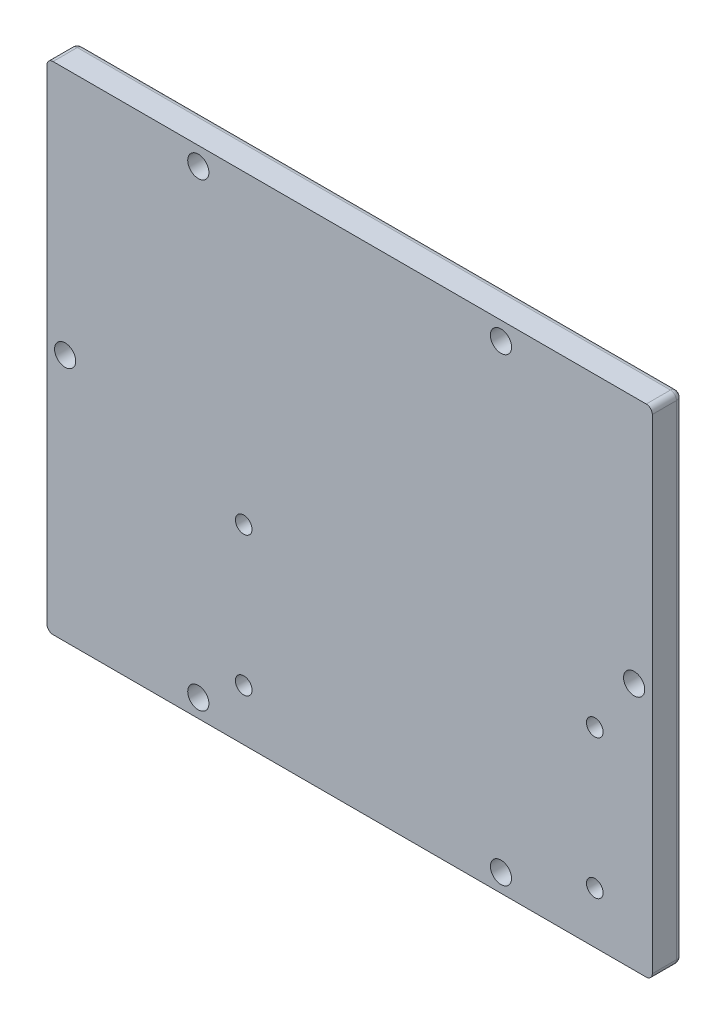
SolidWorks part; units mm, degrees
ref_plane "Plan de face" through (0, 0, 0) normal (0, 0, 1) x (1, 0, 0)
ref_plane "Plan de dessus" through (0, 0, 0) normal (0, 1, 0) x (1, 0, 0)
ref_plane "Plan de droite" through (0, 0, 0) normal (1, 0, 0) x (0, 0, -1)
sketch "Esquisse1" plane through (0, 0, 0) normal (0, 0, 1) x (1, 0, 0)
  line L1 (-50, -41) -> (50, -41)
  line L2 (-50, -41) -> (-50, 41)
  line L3 (-50, 41) -> (50, 41)
  line L4 (50, -41) -> (50, 41)
  line L5 (-50, -41) -> (50, 41) construction
  line L6 (-50, 41) -> (50, -41) construction
  point P0 (0, 0)
  dimension "D1" = 82
  dimension "D2" = 100
extrude "Boss.-Extru.1" add sketch "Esquisse1" along normal blind 5
sketch "Esquisse2" plane through (0, 0, 0) normal (0, 0, 1) x (1, 0, 0)
  line L0 (-81.9731, -38) -> (83.9393, -38) construction
  line L1 (-50, -41) -> (50, -41) construction
  line L2 (0, 0) -> (0, -49.9002) construction
  line L3 (-50, 41) -> (-50, -41) construction
  line L5 (-25, 38) -> (82.6895, 38) construction
  line L6 (50, 41) -> (-50, 41) construction
  circle A0 centre (-25, -38) radius 1.75
  circle A1 centre (25, -38) radius 1.75
  circle A2 centre (-25, 38) radius 1.75
  circle A3 centre (25, 38) radius 1.75
  dimension "D2" = 3.5
  dimension "D4" = 3
  dimension "D5" = 25
  dimension "D1" = 3
  dimension "D3" = 25
extrude "Enlèv. mat.-Extru.1" cut sketch "Esquisse2" along normal up to surface (5 mm away) up to face at (0, 0, 5)
sketch "Esquisse3" plane through (0, 0, 0) normal (0, 0, 1) x (1, 0, 0)
  line L0 (-84.0905, 0) -> (94.0725, 0) construction
  line L1 (47, 56.9426) -> (47, -50.5904) construction
  line L2 (50, -41) -> (50, 41) construction
  circle A0 centre (47, 0) radius 1.75
  dimension "D2" = 3.5
  dimension "D1" = 3
extrude "Enlèv. mat.-Extru.2" cut sketch "Esquisse3" along normal up to surface (5 mm away) up to face at (23.25, -38, 5)
mirror "Symétrie1" about plane through (0, 0, 0) normal (1, 0, 0) of "Enlèv. mat.-Extru.2"
sketch "Esquisse5" [suppressed] plane through (0, 0, 0) normal (0, 0, 1) x (1, 0, 0)
  line L1 (-30.25, -28.75) -> (30.25, -28.75)
  line L2 (-30.25, -28.75) -> (-30.25, 6.75)
  line L3 (-30.25, 6.75) -> (30.25, 6.75)
  line L4 (30.25, -28.75) -> (30.25, 6.75)
  line L5 (-30.25, -28.75) -> (30.25, 6.75) construction
  line L6 (-30.25, 6.75) -> (30.25, -28.75) construction
  line L7 (-50, -41) -> (50, -41) construction
  line L8 (50, -41) -> (50, 41) construction
  point P0 (0, -11)
  dimension "D1" = 60.5
  dimension "D2" = 35.5
  dimension "D3" = 19.75
  dimension "D4" = 30
extrude "Enlèv. mat.-Extru.4" [suppressed] cut sketch "Esquisse5" along normal up to surface (5 mm away)
sketch "Esquisse7" [suppressed] plane through (0, 0, 5) normal (0, 0, 1) x (1, 0, 0)
  line L0 (50, 41) -> (-50, 41) construction
  line L1 (-7, 11) -> (7, 11) construction
  line L2 (-7, 11) -> (-7, 21) construction
  line L3 (-7, 21) -> (7, 21) construction
  line L4 (7, 11) -> (7, 21) construction
  line L5 (-7, 11) -> (7, 21) construction
  line L6 (-7, 21) -> (7, 11) construction
  line L11 (50, -41) -> (50, 41) construction
  circle A3 centre (-7, 11) radius 1.5
  circle A4 centre (7, 11) radius 1.5
  circle A5 centre (-1.66, 20.3) radius 3.65
  dimension "D1" = 7.3
  dimension "D2" = 5.34
  dimension "D4" = 3
  dimension "D6" = 30
  dimension "D5" = 9.3
  dimension "D3" = 8.66
  dimension "D7" = 43
extrude "Enlèv. mat.-Extru.5" [suppressed] cut sketch "Esquisse7" against normal up to surface (5 mm away)
fillet "Congé1" [suppressed] radius 1
fillet "Congé2" radius 1 14 edges at (0, 41, 0) (-50, 0, 0) (0, -41, 0) (50, 0, 0) (-23.25, -38, 0) (26.75, 38, 0) (-23.25, 38, 0) (26.75, -38, 0) (48.75, 0, 0) (-48.75, 0, 0) (50, 41, 2.5) (50, -41, 2.5) (-50, -41, 2.5) (-50, 41, 2.5)
sketch "Esquisse8" plane through (0, 0, 0) normal (0, 0, -1) x (-1, 0, 0)
  line L0 (-50, -40) -> (-50, 40) construction
  line L1 (-40.5, -32.5) -> (17.5, -32.5) construction
  line L2 (-40.5, -32.5) -> (-40.5, -9.5) construction
  line L3 (-40.5, -9.5) -> (17.5, -9.5) construction
  line L4 (17.5, -32.5) -> (17.5, -9.5) construction
  line L5 (-40.5, -32.5) -> (17.5, -9.5) construction
  line L6 (-40.5, -9.5) -> (17.5, -32.5) construction
  line L7 (49, -41) -> (-49, -41) construction
  circle A0 centre (-40.5, -9.5) radius 1.375
  circle A1 centre (17.5, -9.5) radius 1.375
  circle A2 centre (17.5, -32.5) radius 1.375
  circle A3 centre (-40.5, -32.5) radius 1.375
  point P0 (-11.5, -21)
  dimension "D5" = 2.75
  dimension "D1" = 58
  dimension "D2" = 23
  dimension "D3" = 9.5
  dimension "D4" = 8.5
extrude "Enlèv. mat.-Extru.6" cut sketch "Esquisse8" against normal up to surface (5 mm away) up to face at (-48.75, 0, 5)
